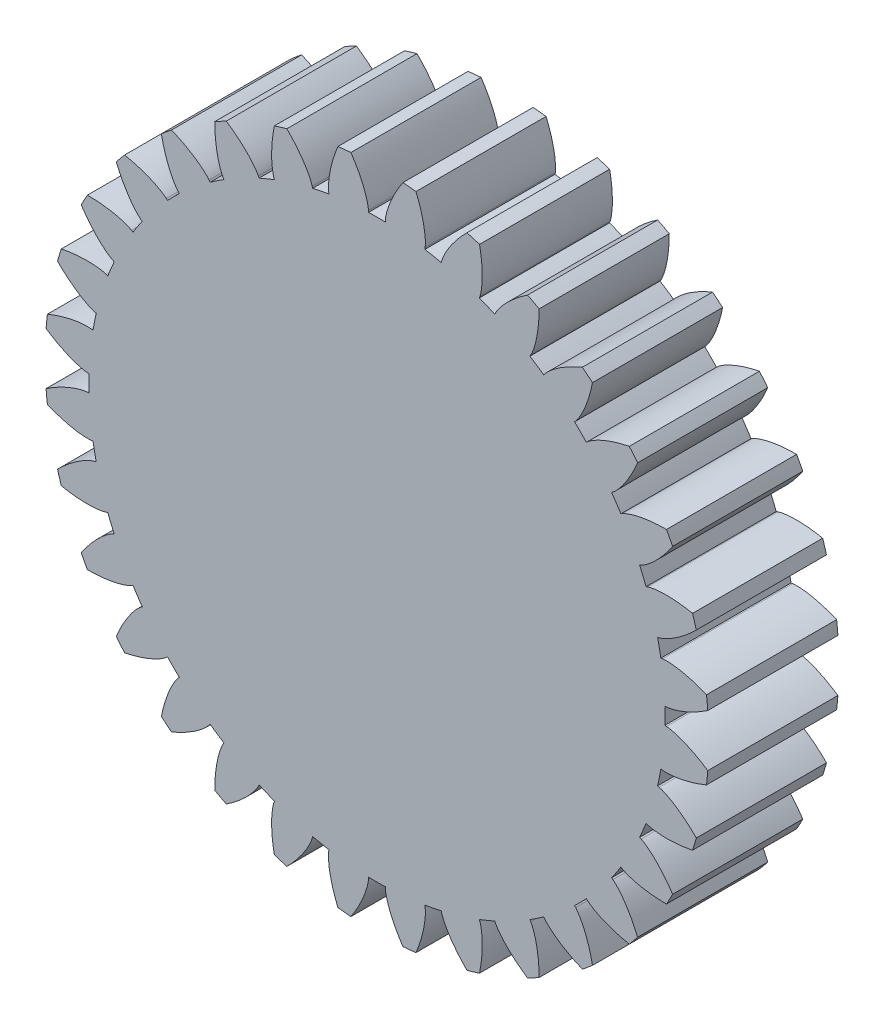
SolidWorks part; units mm, degrees
ref_plane "Front Plane" through (0, 0, 0) normal (0, 0, 1) x (1, 0, 0)
ref_plane "Top Plane" through (0, 0, 0) normal (0, 1, 0) x (1, 0, 0)
ref_plane "Right Plane" through (0, 0, 0) normal (1, 0, 0) x (0, 0, -1)
ref_axis "Axis1" through (0, 0, 71.2135) along (0, 0, -1)
sketch "Sketch1" plane through (0, 0, 0) normal (0, 0, 1) x (1, 0, 0)
  circle A0 centre (0, 0) radius 44.25
  circle A1 centre (0, 0) radius 44.5048
  circle A2 centre (0, 0) radius 45
  circle A3 centre (0, 0) radius 48
  circle A4 centre (0, 0) radius 51
  dimension "Pitch" = 96
  dimension "Addendum" = 102
  dimension "Clearance" = 90
  dimension "Base" = 89.0097
  dimension "Root" = 88.5
extrude "Boss-Extrude1" add sketch "Sketch1" along normal blind 20 contours A4
sketch "Sketch3" plane through (0, 0, 0) normal (0, 0, 1) x (1, 0, 0)
  line L0 (1.292, 44.4861) -> (0, 0) construction
  line L1 (4.7784, 44.2476) -> (0, 0) construction
  line L2 (8.2353, 43.7362) -> (0, 0) construction
  line L3 (11.6414, 42.9553) -> (0, 0) construction
  line L4 (14.9758, 41.9095) -> (0, 0) construction
  line L5 (18.2178, 40.6053) -> (0, 0) construction
  line L6 (21.3475, 39.0508) -> (0, 0) construction
  line L7 (24.3455, 37.2555) -> (0, 0) construction
  line L8 (27.1935, 35.2305) -> (0, 0) construction
  line L9 (29.8739, 32.9884) -> (0, 0) construction
  line L10 (32.37, 30.5428) -> (0, 0) construction
  line L11 (4.7784, 44.2476) -> (1.3032, 44.6229) construction
  line L12 (32.37, 30.5428) -> (8.3818, 55.9661) construction
  line L13 (8.2353, 43.7362) -> (1.3652, 45.0298) construction
  line L14 (11.6414, 42.9553) -> (1.5203, 45.6982) construction
  line L15 (14.9758, 41.9095) -> (1.8095, 46.6143) construction
  line L16 (18.2178, 40.6053) -> (2.2721, 47.7594) construction
  line L17 (21.3475, 39.0508) -> (2.9452, 49.1106) construction
  line L18 (24.3455, 37.2555) -> (3.8633, 50.6402) construction
  line L19 (27.1935, 35.2305) -> (5.0575, 52.3167) construction
  line L20 (29.8739, 32.9884) -> (6.5558, 54.1049) construction
  line L21 (0, 0) -> (0, 48) construction
  line L22 (0, 0) -> (2.3552, 47.9422)
  line L23 (0, 0) -> (-2.3552, 47.9422)
  line L24 (1.292, 44.4861) -> (1.2846, 44.2313)
  line L25 (-1.292, 44.4861) -> (-1.2846, 44.2313)
  circle A0 centre (0, 0) radius 44.5048 construction
  circle A1 centre (0, 0) radius 48 construction
  arc A2 (32.37, 30.5428) -> (1.292, 44.4861) centre (0, 0) ccw construction
  circle A3 centre (0, 0) radius 44.25 construction
  circle A4 centre (0, 0) radius 44.25
  circle A5 centre (0, 0) radius 51 construction
  circle A6 centre (0, 0) radius 51
  spline S0 degree 3 poles (1.292, 44.4861) (1.3028, 44.6688) (1.3661, 45.0764) (1.5341, 45.7893) (1.8273, 46.7052) (2.5178, 48.4004) (3.6009, 50.322) (5.5964, 53.1141) (7.185, 54.8359) (8.3818, 55.9661) knots 0 0 0 0 0.040008 0.090018 0.16003 0.250047 0.489907 0.639935 1 1 1 1
  spline S1 degree 3 poles (-1.292, 44.4861) (-1.3028, 44.6688) (-1.3661, 45.0764) (-1.5341, 45.7893) (-1.8273, 46.7052) (-2.5178, 48.4004) (-3.6009, 50.322) (-5.5964, 53.1141) (-7.185, 54.8359) (-8.3818, 55.9661) knots 0 0 0 0 0.040008 0.090018 0.16003 0.250047 0.489907 0.639935 1 1 1 1
  point P2 (0, 0)
  point P18 (0, 0)
  point P57 (3.4733, 44.1443)
  dimension "D2" = 45
  dimension "D3" = 3.4954
  dimension "D4" = 34.954
  dimension "D5" = 6.9908
  dimension "D6" = 10.4862
  dimension "D7" = 13.9816
  dimension "D8" = 17.477
  dimension "D9" = 20.9724
  dimension "D10" = 24.4678
  dimension "D11" = 27.9632
  dimension "D12" = 31.4586
  dimension "D13" = 5.625
  dimension "D1" = 11
extrude "Cut-Extrude3" cut sketch "Sketch3" along normal through all contours S1 L25 A4 L24 S0 A6 region at (0, 48.2743, 0)
pattern_circular "CirPattern1" count 32 over 360 about axis through (0, 0, 71.2135) along (0, 0, -1) of "Cut-Extrude3"
equation "\"Module\"= 3"
equation "\"numTeeth\"= 32"
equation "\"pressureAngle\"= 22deg"
equation "\"toothRadius\"= 0.2"
equation "\"Pitch@Sketch1\"=\"Module\"*\"numTeeth\""
equation "\"Addendum@Sketch1\"=\"Pitch@Sketch1\"+\"Module\"*2"
equation "\"Clearance@Sketch1\"=\"Pitch@Sketch1\"-\"Module\"*2"
equation "\"Base@Sketch1\"=\"Pitch@Sketch1\"*cos(\"pressureAngle\")"
equation "\"Root@Sketch1\"=\"Pitch@Sketch1\"-\"Module\"*1.25*2"
equation "\"D4@Sketch3\"= \"Base@Sketch1\" * pi / 8"
equation "\"D3@Sketch3\"= \"D4@Sketch3\" / 10"
equation "\"D5@Sketch3\"=\"D3@Sketch3\"*2"
equation "\"D6@Sketch3\"=\"D3@Sketch3\"*3"
equation "\"D7@Sketch3\"=\"D3@Sketch3\"*4"
equation "\"D8@Sketch3\"=\"D3@Sketch3\"*5"
equation "\"D9@Sketch3\"=\"D3@Sketch3\"*6"
equation "\"D10@Sketch3\"=\"D3@Sketch3\"*7"
equation "\"D11@Sketch3\"=\"D3@Sketch3\"*8"
equation "\"D12@Sketch3\"=\"D3@Sketch3\"*9"
equation "\"D13@Sketch3\"=180/\"numTeeth\""
equation "\"D1@CirPattern1\"=\"numTeeth\""
